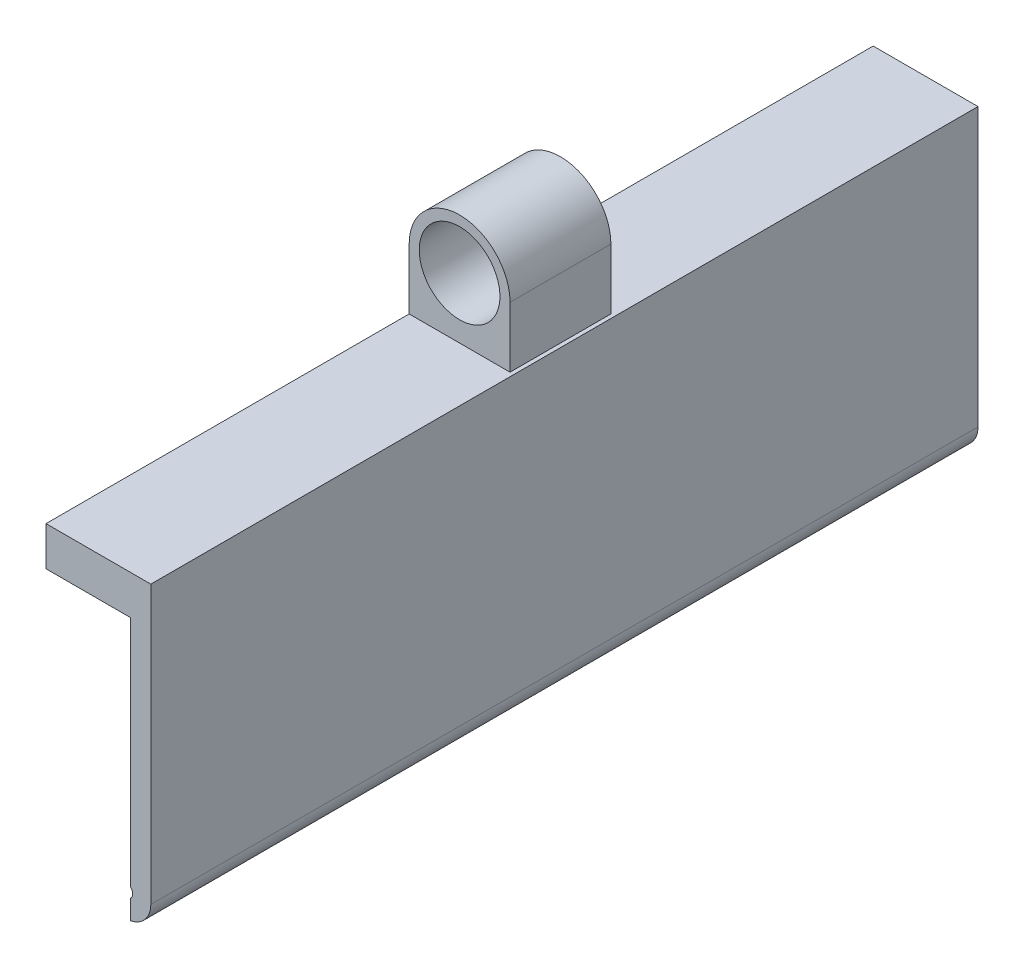
SolidWorks part; units mm, degrees
ref_plane "Front Plane" through (0, 0, 0) normal (0, 0, 1) x (1, 0, 0)
ref_plane "Top Plane" through (0, 0, 0) normal (0, 1, 0) x (1, 0, 0)
ref_plane "Right Plane" through (0, 0, 0) normal (1, 0, 0) x (0, 0, -1)
sketch "Sketch1" plane through (0, 0, 0) normal (0, 0, 1) x (1, 0, 0)
  line L0 (0, 0) -> (3.1723, 0) construction
  line L1 (2.44, 0) -> (2.44, 25)
  line L2 (0.44, 4.49) -> (0.44, 25)
  line L3 (0.44, 25) -> (2.44, 25)
  circle A0 centre (0, 0) radius 0.64
  arc A1 (-1.0175, 2.2177) -> (2.44, 0) centre (0, 0) ccw
  arc A2 (0.44, 4.49) -> (-1.0175, 2.2177) centre (-2.06, 4.49) cw
  dimension "D1" = 1.28
  dimension "D2" = 4.88
  dimension "D5" = 2.5
  dimension "D3" = 25
  dimension "D4" = 2
extrude "Boss-Extrude1" add sketch "Sketch1" along normal blind 82
sketch "Sketch3" plane through (0, 25, 0) normal (0, 1, 0) x (1, 0, 0)
  line L1 (0.44, -82) -> (2.44, -82)
  line L2 (0.44, -82) -> (0.44, 0)
  line L3 (0.44, 0) -> (2.44, 0)
  line L4 (2.44, -82) -> (2.44, 0)
extrude "Boss-Extrude4" add sketch "Sketch3" along normal blind 2.5
sketch "Sketch6" plane through (0.44, 0, 0) normal (-1, 0, 0) x (0, 0, 1)
  line L1 (82, 27.5) -> (0, 27.5)
  line L2 (82, 27.5) -> (82, 23.6193)
  line L3 (82, 23.6193) -> (0, 23.6193)
  line L4 (0, 27.5) -> (0, 23.6193)
  dimension "D1" = 23.01
extrude "Boss-Extrude5" add sketch "Sketch6" along normal blind 8.39
ref_plane "Plane2" through (-7.95, 23.6193, 0) normal (0, 0, 1) x (1, 0, 0)
ref_plane "Plane3" through (-7.95, 23.6193, 82) normal (0, 0, 1) x (1, 0, 0)
ref_plane "Plane4" through (0.44, 23.6193, 82) normal (0, 0, 1) x (1, 0, 0)
sketch "Sketch8" plane through (0, 0, 0) normal (0, 0, -1) x (-1, 0, 0)
  line L0 (7.95, 27.5) -> (7.95, 33.5)
  line L1 (-2.05, 33.5) -> (-2.05, 27.5)
  line L2 (-2.44, 27.5) -> (7.95, 27.5) construction
  line L3 (7.95, 27.5) -> (-2.05, 27.5)
  circle A0 centre (2.95, 33.5) radius 4
  arc A1 (7.95, 33.5) -> (-2.05, 33.5) centre (2.95, 33.5) ccw
extrude "Boss-Extrude6" add sketch "Sketch8" against normal blind 10 from offset 36 offset against normal yes
sketch "Sketch9" plane through (0, 0, 0) normal (0, 0, -1) x (-1, 0, 0)
  line L0 (-0.44, 23.6193) -> (-0.44, 4.49) construction
  line L1 (-0.44, 5.1517) -> (4.56, 5.1517)
  line L2 (-0.44, 5.1517) -> (-0.44, -2.44)
  line L3 (-0.44, -2.44) -> (4.56, -2.44)
  line L4 (4.56, 5.1517) -> (4.56, -2.44)
  dimension "D1" = 7.5917
  dimension "D2" = 5
extrude "Cut-Extrude1" cut sketch "Sketch9" against normal blind 62 from offset 10 offset against normal yes
extrude "Cut-Extrude2" cut sketch "Sketch9<2>" against normal blind 5
sketch "Sketch9<2>" plane through (0, 0, 0) normal (0, 0, -1) x (-1, 0, 0) same geometry as "Sketch9"
extrude "Cut-Extrude3" cut sketch "Sketch9<3>" against normal blind 5 from offset 77 offset against normal yes
sketch "Sketch9<3>" plane through (0, 0, 0) normal (0, 0, -1) x (-1, 0, 0) same geometry as "Sketch9"
